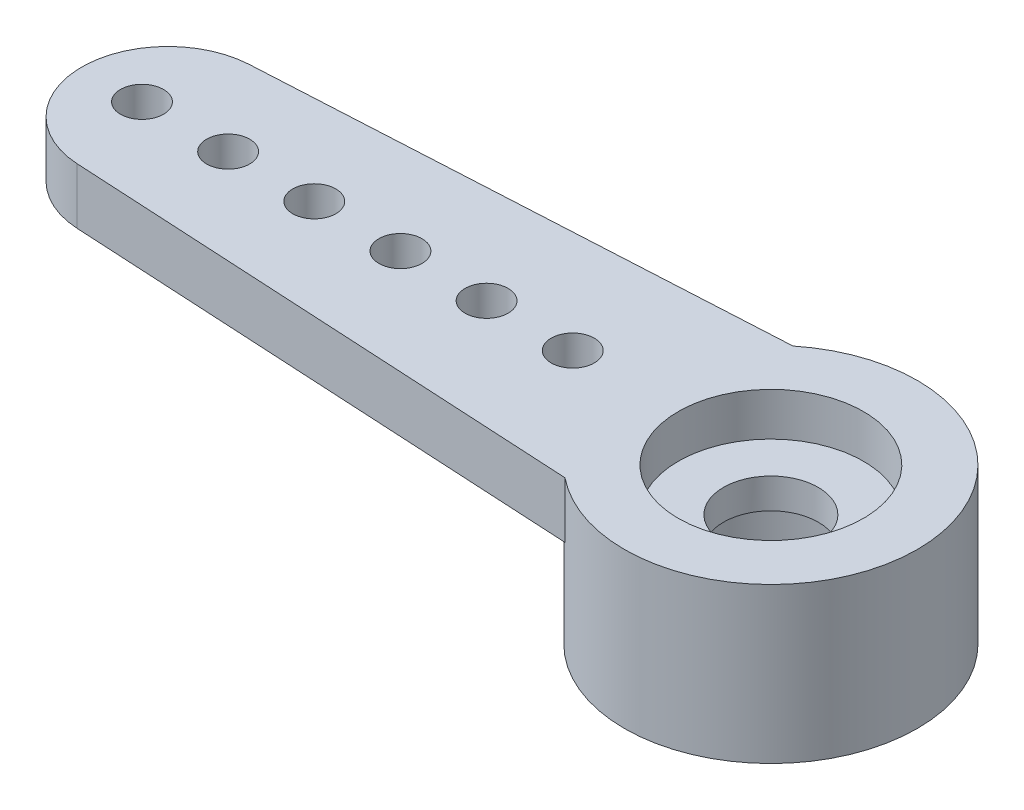
SolidWorks part; units mm, degrees
ref_plane "Płaszczyzna przednia" through (0, 0, 0) normal (0, 0, 1) x (1, 0, 0)
ref_plane "Płaszczyzna górna" through (0, 0, 0) normal (0, 1, 0) x (1, 0, 0)
ref_plane "Płaszczyzna prawa" through (0, 0, 0) normal (1, 0, 0) x (0, 0, -1)
sketch "Sketch1" plane through (0, 0, 0) normal (0, 1, 0) x (1, 0, 0)
  line L9 (3.7667, 8.32) -> (-8.2085, 7.6696)
  line L10 (-8.2085, 3.6754) -> (3.7667, 3.025)
  circle A1 centre (-8.7, 5.6725) radius 0.5
  arc A9 (3.7667, 3.025) -> (3.7667, 8.32) centre (5.9, 5.6725) ccw
  arc A10 (-8.2085, 7.6696) -> (-8.2085, 3.6754) centre (-8.1, 5.6725) ccw
  circle A13 centre (1.3, 5.6725) radius 0.5
  circle A14 centre (-0.7, 5.6725) radius 0.5
  circle A15 centre (-2.7, 5.6725) radius 0.5
  circle A16 centre (-4.7, 5.6725) radius 0.5
  circle A17 centre (-6.7, 5.6725) radius 0.5
  circle A19 centre (5.9, 5.6725) radius 1.1
  dimension "D1" = 1
  dimension "D2" = 2.2
  dimension "D3" = 3.4
  dimension "D4" = 2
  dimension "D5" = 1.3
  dimension "D6" = 3.7667
  dimension "D7" = 5.9
  dimension "D8" = 0.7
  dimension "D9" = 2.7
  dimension "D10" = 4.7
  dimension "D11" = 6.7
  dimension "D12" = 8.1
  dimension "D13" = 3.025
  dimension "D14" = 8.7
extrude "Boss-Extrude1" add sketch "Sketch1" against normal blind 1.3
sketch "Sketch3" plane through (0, 0, 0) normal (0, 1, 0) x (1, 0, 0)
  circle A1 centre (5.9, 5.6725) radius 2.15
  circle A3 centre (5.9, 5.6725) radius 1.1 construction
  dimension "D1" = 4.3
extrude "Cut-Extrude1" cut sketch "Sketch3" against normal blind 1
sketch "Sketch4" plane through (0, -1.3, 0) normal (0, -1, 0) x (1, 0, 0)
  circle A1 centre (5.9, -5.6725) radius 3.4
  circle A2 centre (1.3, -5.6725) radius 0.5 construction
  point P0 (5.9, -5.6725)
  point P3 (5.596, 1.1199)
  dimension "D1" = 6.8
  dimension "D2" = 4.296
  dimension "D3" = 6.7924
extrude "Boss-Extrude3" add sketch "Sketch4" along normal offset from surface (2.3 mm away) 3.6 up to face at (5.9, 0, -3.5225)
sketch "Sketch5" plane through (0, -3.6, 0) normal (0, -1, 0) x (1, 0, 0)
  circle A1 centre (5.9, -5.6725) radius 2.35
  arc A3 (3.7667, -8.32) -> (3.7667, -3.025) centre (5.9, -5.6725) ccw construction
  dimension "D1" = 4.7
extrude "Cut-Extrude2" cut sketch "Sketch5" against normal blind 1.9
sketch "Sketch6" plane through (0, -1.3, 0) normal (0, 1, 0) x (1, 0, 0)
  circle A1 centre (5.9, 5.6725) radius 1.1
  circle A2 centre (5.9, 5.6725) radius 1.1
  dimension "D1" = 0
extrude "Cut-Extrude3" cut sketch "Sketch6" against normal up to next
ref_axis "os obrotu" through (5.9, -9.5043, -5.6725) along (0, 1, 0)
ref_axis "Axis2" through (-11.9132, 0, -5.6725) along (1, 0, 0)
